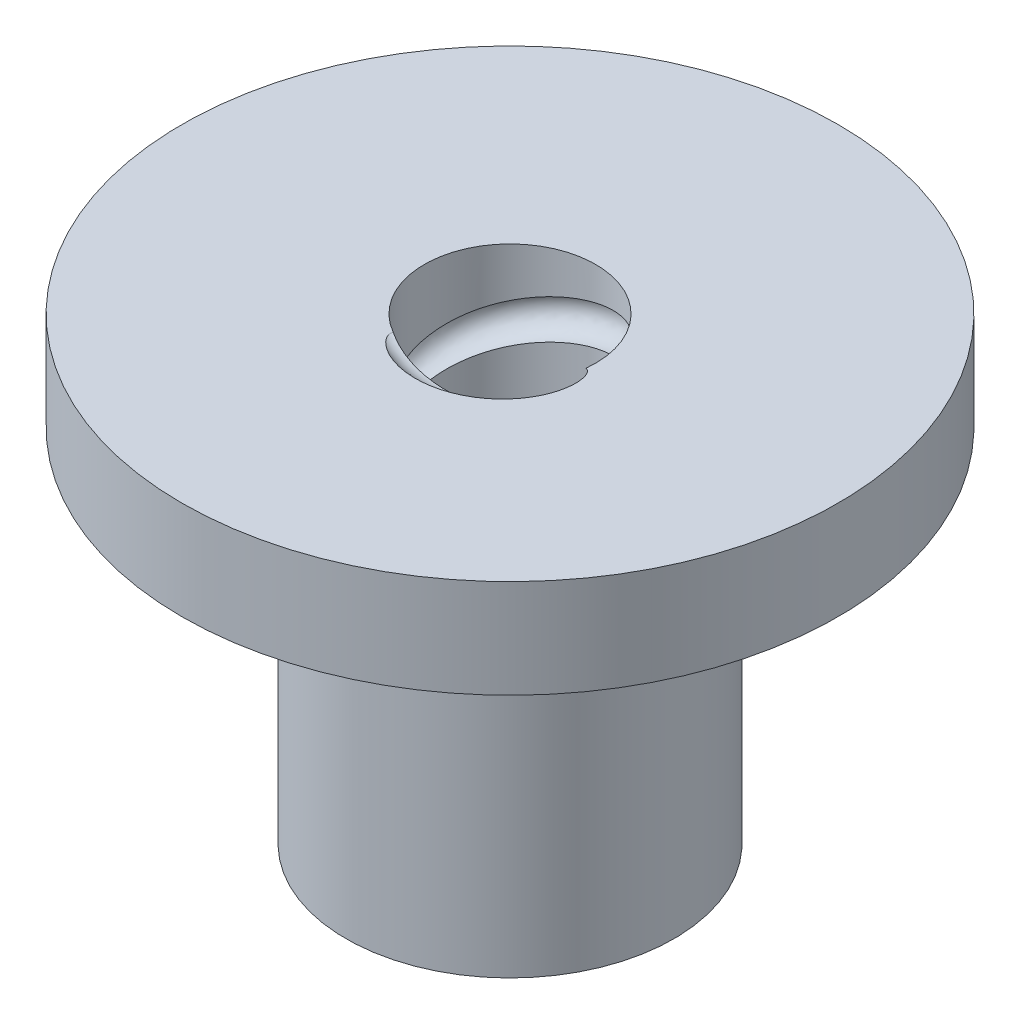
SolidWorks part; units mm, degrees
ref_plane "Front Plane" through (0, 0, 0) normal (0, 0, 1) x (1, 0, 0)
ref_plane "Top Plane" through (0, 0, 0) normal (0, 1, 0) x (1, 0, 0)
ref_plane "Right Plane" through (0, 0, 0) normal (1, 0, 0) x (0, 0, -1)
sketch "Sketch1" plane through (0, 0, 0) normal (0, 1, 0) x (1, 0, 0)
  circle A0 centre (0, 0) radius 50
  dimension "D2" = 100
extrude "Boss-Extrude1" add sketch "Sketch1" along normal blind 15
sketch "Sketch2" plane through (0, 0, 0) normal (0, -1, 0) x (1, 0, 0)
  circle A0 centre (0, 0) radius 25
  dimension "D1" = 50
extrude "Boss-Extrude2" add sketch "Sketch2" along normal blind 55
sketch "Sketch3" plane through (0, 15, 0) normal (0, 1, 0) x (1, 0, 0)
  circle A0 centre (0, 0) radius 13.05
  dimension "D1" = 26.1
extrude "Cut-Extrude1" cut sketch "Sketch3" against normal blind 55
sketch "Sketch5" plane through (0, -55, 0) normal (0, 1, 0) x (1, 0, 0)
  circle A0 centre (0, 0) radius 13.05 construction
  circle A1 centre (0, 0) radius 13.05
curve "Helix/Spiral1" pitch 19.05 height 70 turns 3.6745
sketch "Sketch6" plane through (0, 0, 0) normal (0, 0, 1) x (1, 0, 0)
  circle A0 centre (-13.05, -55) radius 3
  spline S0 degree 3 poles (1979.8834, 105.3129) (300.8813, -81.8835) (-43.924, -66.7804) (-9.4924, -52.6274) (-5.1743, -51.4406) (-0.0739, -50.2543) (5.0376, -49.0678) (9.3876, -47.8814) (12.3182, -46.6949) (13.3865, -45.5085) (12.431, -44.322) (9.596, -43.1356) (5.3103, -41.9492) (0.2217, -40.7627) (-4.9004, -39.5763) (-9.2816, -38.3898) (-12.2596, -37.2034) (-13.3841, -36.0169) (-12.4851, -34.8305) (-9.6985, -33.6441) (-5.4456, -32.4576) (-0.3695, -31.2712) (4.7626, -30.0847) (9.1745, -28.8983) (12.1995, -27.7119) (13.38, -26.5254) (12.5376, -25.339) (9.7998, -24.1525) (5.5803, -22.9661) (0.5172, -21.7797) (-4.6241, -20.5932) (-9.0663, -19.4068) (-12.1378, -18.2203) (-13.3743, -17.0339) (-12.5887, -15.8475) (-9.8999, -14.661) (-5.7143, -13.4746) (-0.6649, -12.2881) (4.4851, -11.1017) (8.957, -9.9153) (12.0748, -8.7288) (13.3669, -7.5424) (12.6382, -6.3559) (9.9988, -5.1695) (5.8476, -3.9831) (0.8124, -2.7966) (-4.3456, -1.6102) (-8.8466, -0.4237) (-12.0102, 0.7627) (-13.358, 1.9492) (-12.6862, 3.1356) (-10.0964, 4.322) (-5.9802, 5.5085) (-0.9599, 6.6949) (4.2055, 7.8814) (8.7352, 9.0678) (11.9441, 10.2543) (13.3477, 11.4406) (12.7315, 12.6274) (-12.6563, 24.4979) (-257.4643, 36.9091) (2004.1255, -66.0446) knots -0.556429 -0.556429 -0.556429 -0.556429 0.016949 0.033898 0.050847 0.067797 0.084746 0.101695 0.118644 0.135593 0.152542 0.169492 0.186441 0.20339 0.220339 0.237288 0.254237 0.271186 0.288136 0.305085 0.322034 0.338983 0.355932 0.372881 0.389831 0.40678 0.423729 0.440678 0.457627 0.474576 0.491525 0.508475 0.525424 0.542373 0.559322 0.576271 0.59322 0.610169 0.627119 0.644068 0.661017 0.677966 0.694915 0.711864 0.728814 0.745763 0.762712 0.779661 0.79661 0.813559 0.830508 0.847458 0.864407 0.881356 0.898305 0.915254 0.932203 0.949153 0.966102 0.983051 1.458491 1.458491 1.458491 1.458491 only from (-13.05, -55) to (5.9581, 15) construction
  spline S1 degree 3 poles (-13.05, -55) (-13.05, -54.6069) (-12.3753, -53.8125) (-9.4924, -52.6274) (-5.1743, -51.4406) (-0.0739, -50.2543) (5.0376, -49.0678) (9.3876, -47.8814) (12.3182, -46.6949) (13.3865, -45.5085) (12.431, -44.322) (9.596, -43.1356) (5.3103, -41.9492) (0.2217, -40.7627) (-4.9004, -39.5763) (-9.2816, -38.3898) (-12.2596, -37.2034) (-13.3841, -36.0169) (-12.4851, -34.8305) (-9.6985, -33.6441) (-5.4456, -32.4576) (-0.3695, -31.2712) (4.7626, -30.0847) (9.1745, -28.8983) (12.1995, -27.7119) (13.38, -26.5254) (12.5376, -25.339) (9.7998, -24.1525) (5.5803, -22.9661) (0.5172, -21.7797) (-4.6241, -20.5932) (-9.0663, -19.4068) (-12.1378, -18.2203) (-13.3743, -17.0339) (-12.5887, -15.8475) (-9.8999, -14.661) (-5.7143, -13.4746) (-0.6649, -12.2881) (4.4851, -11.1017) (8.957, -9.9153) (12.0748, -8.7288) (13.3669, -7.5424) (12.6382, -6.3559) (9.9988, -5.1695) (5.8476, -3.9831) (0.8124, -2.7966) (-4.3456, -1.6102) (-8.8466, -0.4237) (-12.0102, 0.7627) (-13.358, 1.9492) (-12.6862, 3.1356) (-10.0964, 4.322) (-5.9802, 5.5085) (-0.9599, 6.6949) (4.2055, 7.8814) (8.7352, 9.0678) (11.9441, 10.2543) (13.3477, 11.4406) (12.7315, 12.6274) (10.197, 13.8125) (7.4634, 14.6069) (5.9581, 15) knots 0 0 0 0 0.016949 0.033898 0.050847 0.067797 0.084746 0.101695 0.118644 0.135593 0.152542 0.169492 0.186441 0.20339 0.220339 0.237288 0.254237 0.271186 0.288136 0.305085 0.322034 0.338983 0.355932 0.372881 0.389831 0.40678 0.423729 0.440678 0.457627 0.474576 0.491525 0.508475 0.525424 0.542373 0.559322 0.576271 0.59322 0.610169 0.627119 0.644068 0.661017 0.677966 0.694915 0.711864 0.728814 0.745763 0.762712 0.779661 0.79661 0.813559 0.830508 0.847458 0.864407 0.881356 0.898305 0.915254 0.932203 0.949153 0.966102 0.983051 1 1 1 1
  dimension "D1" = 6
sweep "Cut-Sweep2" cut profiles "Sketch6" path "Helix/Spiral1" align with end faces yes
